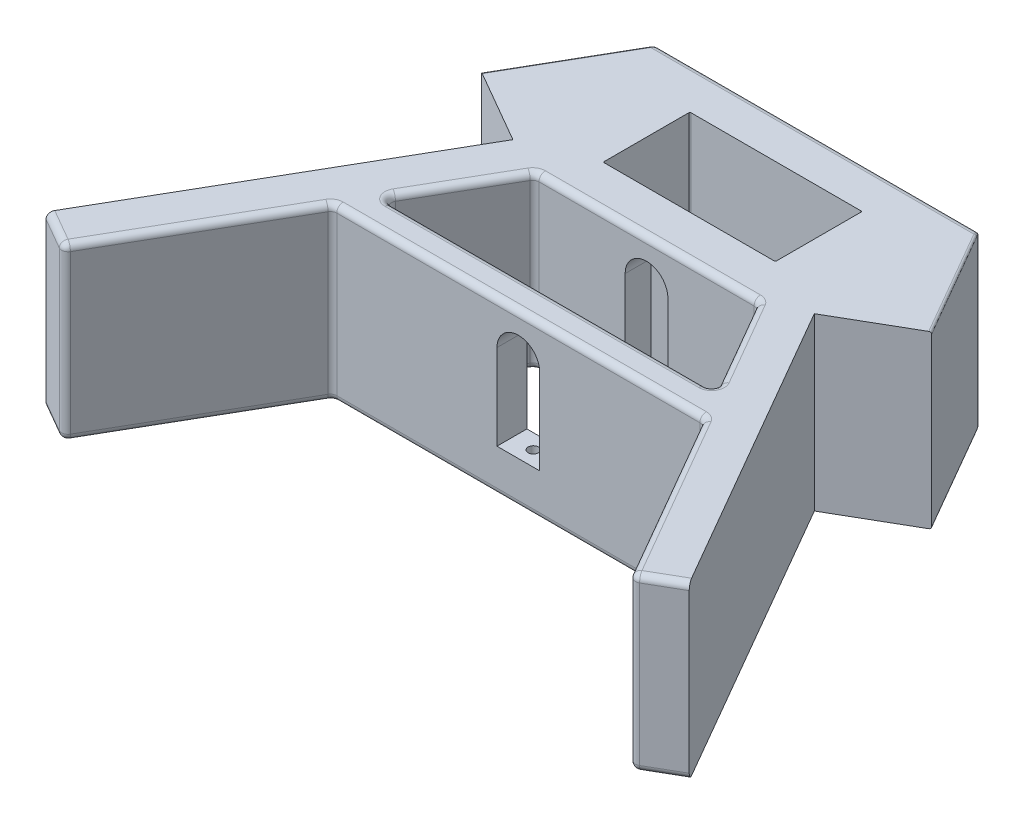
SolidWorks part; units mm, degrees
material "ABS"
ref_plane "Front Plane" through (0, 0, 0) normal (0, 0, 1) x (1, 0, 0)
ref_plane "Top Plane" through (0, 0, 0) normal (0, 1, 0) x (1, 0, 0)
ref_plane "Right Plane" through (0, 0, 0) normal (1, 0, 0) x (0, 0, -1)
sketch "Sketch3" plane through (0, 0, 0) normal (0, 1, 0) x (1, 0, 0)
  line L0 (-52.6837, -6.1) -> (-35.2766, -16.15)
  line L1 (-20.15, 10.15) -> (20.15, 10.15)
  line L2 (-20.15, 10.15) -> (-20.15, -10.15)
  line L3 (-20.15, -10.15) -> (20.15, -10.15)
  line L4 (20.15, 10.15) -> (20.15, -10.15)
  line L5 (-20.15, 10.15) -> (20.15, -10.15) construction
  line L6 (-20.15, -10.15) -> (20.15, 10.15) construction
  line L7 (-35.2766, -16.15) -> (-75.2766, -85.432)
  line L8 (52.6837, -6.1) -> (35.2766, -16.15)
  line L9 (35.2766, -16.15) -> (75.2766, -85.432)
  line L10 (-35.2766, -16.15) -> (35.2766, -16.15) construction
  line L11 (-75.2766, -85.432) -> (75.2766, -85.432) construction
  line L12 (-52.6837, -6.1) -> (52.6837, -6.1) construction
  line L13 (0, 0) -> (0, 50000) construction
  line L14 (-37.5282, 20.15) -> (37.5282, 20.15)
  line L15 (37.5282, 20.15) -> (52.6837, -6.1)
  line L16 (-37.5282, 20.15) -> (-52.6837, -6.1)
  line L17 (-43.9801, -11.125) -> (-25.9235, 20.15) construction
  line L18 (-75.2766, -85.432) -> (-66.6163, -90.432)
  line L19 (-66.6163, -90.432) -> (-43.3595, -50.15)
  line L20 (-43.3595, -50.15) -> (43.3595, -50.15)
  line L21 (43.3595, -50.15) -> (66.6163, -90.432)
  line L22 (66.6163, -90.432) -> (75.2766, -85.432)
  line L23 (-26.039, -20.15) -> (26.039, -20.15)
  line L24 (-21.59, -50.15) -> (21.59, -50.15) construction
  line L25 (-21.59, -50.15) -> (-21.59, -98.15) construction
  line L26 (-21.59, -98.15) -> (21.59, -98.15) construction
  line L27 (21.59, -50.15) -> (21.59, -98.15) construction
  line L28 (-11, -28.15) -> (11, -28.15) construction
  line L29 (-11, -28.15) -> (-11, -45.65) construction
  line L30 (-11, -45.65) -> (11, -45.65) construction
  line L31 (11, -28.15) -> (11, -45.65) construction
  line L32 (26.039, -20.15) -> (39.318, -43.15)
  line L33 (39.318, -43.15) -> (-39.318, -43.15)
  line L34 (-39.318, -43.15) -> (-26.039, -20.15)
  point P0 (0, 0)
  point P15 (0, -85.432)
  point P16 (0, -16.15)
  point P17 (0, -6.1)
  point P21 (0, 20.15)
  point P27 (0, -50.15)
  point P28 (0, -50.15)
  point P37 (0, -28.15)
  dimension "D1" = 40.3
  dimension "D2" = 20.3
  dimension "D3" = 300
  dimension "D4" = 20.1
  dimension "D5" = 80
  dimension "D6" = 10
  dimension "D7" = 10
  dimension "D8" = 6
  dimension "D9" = 10
  dimension "D10" = 43.18
  dimension "D11" = 48
  dimension "D12" = 22
  dimension "D13" = 17.5
  dimension "D14" = 22
  dimension "D15" = 30
  dimension "D16" = 10
  dimension "D17" = 7
extrude "Boss-Extrude1" add sketch "Sketch3" along normal blind 35
extrude "Boss-Extrude3" add sketch "Sketch3<2>" against normal blind 5 contours L21 L22 L9 L8 L15 L14 L16 L0 L7 L18 L19 L20 L1 L4 L3 L2 L33 L34 L23 L32 | L4 L1 L2 L3 region at (-43.4882, 0, -6.091) region at (0, 0, 0)
sketch "Sketch3<2>" plane through (0, 0, 0) normal (0, 1, 0) x (1, 0, 0) same geometry as "Sketch3"
fillet "Fillet2" radius 0.25 4 edges at (-20.15, 17.5, 10.15) (20.15, 17.5, 10.15) (-20.15, 17.5, -10.15) (20.15, 17.5, -10.15)
fillet "Fillet3" radius 1.5 30 edges at (-54.9879, 35, 70.291) (-32.6785, 35, 31.65) (54.9879, -5, 70.291) (0, -5, 20.15) (0, 35, 50.15) (0, 35, 43.15) (0, 35, 20.15) (0, -5, 50.15) (32.6785, -5, 31.65) (-32.6785, -5, 31.65) (0, 35, -20.15) (70.9465, 35, 87.932) (-70.9465, 35, 87.932) (54.9879, 35, 70.291) (32.6785, 35, 31.65) (70.9465, -5, 87.932) (-54.9879, -5, 70.291) (-70.9465, -5, 87.932) (0, -5, -20.15) (0, -5, 43.15) (-66.6163, 15, 90.432) (66.6163, 15, 90.432) (37.5282, 15, -20.15) (-37.5282, 15, -20.15) (-43.3595, 15, 50.15) (43.3595, 15, 50.15) (-39.318, 15, 43.15) (39.318, 15, 43.15) (26.039, 15, 20.15) (-26.039, 15, 20.15)
fillet "Fillet4" radius 0.5 12 edges at (-37.4122, -4.25, -19.949) (-38.1701, -4.9489, -19.0382) (37.4122, -4.25, -19.949) (38.1701, -4.9489, -19.0382) (37.4122, 34.25, -19.949) (38.1701, 34.9489, -19.0382) (-37.4122, 34.25, -19.949) (-38.1701, 34.9489, -19.0382) (-45.539, -5, -6.275) (45.539, -5, -6.275) (45.539, 35, -6.275) (-45.539, 35, -6.275)
sketch "Sketch4" plane through (0, 0, 50.15) normal (0, 0, 1) x (1, 0, 0)
  line L0 (-5, 25) -> (5, 25)
  line L1 (5, 25) -> (5, 5)
  line L2 (-5, 25) -> (-5, 5)
  line L3 (-42.4935, -3.5) -> (42.4935, -3.5) construction
  line L4 (42.4935, -5) -> (-42.4935, -5) construction
  line L5 (-42.4935, 35) -> (42.4935, 35) construction
  line L6 (-5, 5) -> (5, 5)
  arc A0 (5, 5) -> (-5, 5) centre (0, 5) cw
  arc A1 (-5, 25) -> (5, 25) centre (0, 25) cw
  point P2 (0, 25)
  point P7 (0, -3.5)
  dimension "D2" = 10
  dimension "D1" = 10
  dimension "D3" = 10
extrude "Cut-Extrude1" cut sketch "Sketch4" against normal offset from surface (36 mm away) 6 contours A1 L0 | L2 L6 L1 L0 region at (0, 27.1221, 50.15) region at (0, 15, 50.15) up to face at (0, 15, 20.15) offset beyond the face yes
sketch "Sketch5" plane through (0, -5, 0) normal (0, 1, 0) x (1, 0, 0)
  line L0 (36.72, -44.65) -> (-36.72, -44.65) construction
  line L1 (1.198, -44.575) -> (-1.198, -44.575)
  line L2 (-1.198, -44.575) -> (-2.396, -46.65)
  line L3 (-2.396, -46.65) -> (-1.198, -48.725)
  line L4 (-1.198, -48.725) -> (1.198, -48.725)
  line L5 (1.198, -48.725) -> (2.396, -46.65)
  line L6 (2.396, -46.65) -> (1.198, -44.575)
  line L8 (2.7453, -44.65) -> (2.7453, -48.65) construction
  line L9 (-42.4935, -48.65) -> (42.4935, -48.65) construction
  line L10 (169.2257, -171.7155) -> (166.8297, -171.7155)
  line L11 (166.8297, -171.7155) -> (165.6317, -173.7905)
  line L12 (165.6317, -173.7905) -> (166.8297, -175.8655)
  line L13 (166.8297, -175.8655) -> (169.2257, -175.8655)
  line L14 (169.2257, -175.8655) -> (170.4237, -173.7905)
  line L15 (170.4237, -173.7905) -> (169.2257, -171.7155)
  line L16 (170.773, -171.7905) -> (170.773, -175.7905) construction
  line L17 (0, -10.15) -> (0, -18.65) construction
  line L18 (2.396, -17.65) -> (1.198, -15.575)
  line L19 (1.198, -15.575) -> (-1.198, -15.575)
  line L20 (-1.198, -15.575) -> (-2.396, -17.65)
  line L21 (-2.396, -17.65) -> (-1.198, -19.725)
  line L22 (-1.198, -19.725) -> (1.198, -19.725)
  line L23 (1.198, -19.725) -> (2.396, -17.65)
  line L24 (-19.9, -10.15) -> (19.9, -10.15) construction
  line L25 (-25.1729, -18.65) -> (25.1729, -18.65) construction
  line L26 (25.1729, -20.15) -> (-25.1729, -20.15) construction
  line L27 (-5, -50.15) -> (5, -50.15) construction
  circle A0 centre (0, -46.65) radius 1.2
  circle A1 centre (0, -46.65) radius 2.075 construction
  circle A2 centre (168.0277, -173.7905) radius 1.2
  circle A3 centre (168.0277, -173.7905) radius 2.075 construction
  circle A4 centre (0, -17.65) radius 1.2
  circle A5 centre (0, -17.65) radius 2.075 construction
  point P2 (0, -48.725)
  point P10 (0, -44.575)
  point P13 (2.7453, -46.65)
  point P14 (0, 0)
  point P15 (0, 0)
  point P23 (168.0277, -175.8655)
  point P31 (168.0277, -171.7155)
  point P32 (170.773, -173.7905)
  point P53 (0, -50.15)
  dimension "D2" = 2.4
  dimension "D4" = 2.4
  dimension "D6" = 2.4
  dimension "D1" = 4.15
  dimension "D3" = 4.15
  dimension "D5" = 4.15
  dimension "D7" = 2.5
extrude "Cut-Extrude2" cut sketch "Sketch5" along normal blind 10 contours A0 | A4
extrude "Cut-Extrude3" cut sketch "Sketch5<3>" along normal blind 1.6 contours L5 L6 L1 L2 L3 L4 | L18 L19 L20 L21 L22 L23
sketch "Sketch5<3>" plane through (0, -5, 0) normal (0, 1, 0) x (1, 0, 0) same geometry as "Sketch5"
